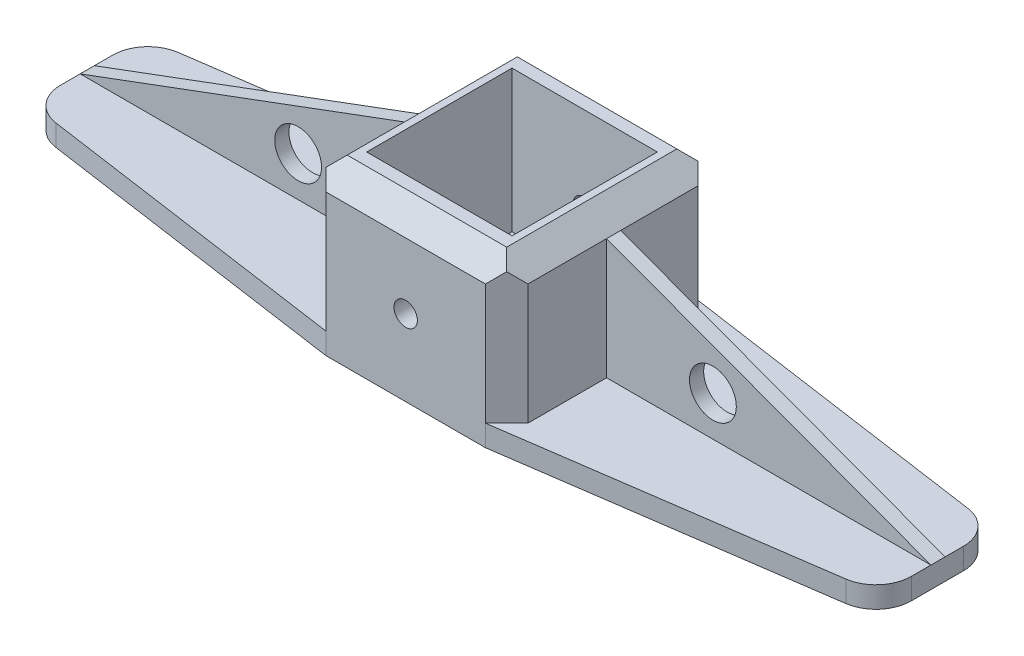
SolidWorks part; units mm, degrees
ref_plane "Front Plane" through (0, 0, 0) normal (0, 0, 1) x (1, 0, 0)
ref_plane "Top Plane" through (0, 0, 0) normal (0, 1, 0) x (1, 0, 0)
ref_plane "Right Plane" through (0, 0, 0) normal (1, 0, 0) x (0, 0, -1)
sketch "Sketch1" plane through (0, 0, 0) normal (0, 1, 0) x (1, 0, 0)
  line L1 (-60, 15) -> (60, 15)
  line L2 (-60, 15) -> (-60, -15)
  line L3 (-60, -15) -> (60, -15)
  line L4 (60, 15) -> (60, -15)
  line L5 (-60, 15) -> (60, -15) construction
  line L6 (-60, -15) -> (60, 15) construction
  point P0 (0, 0)
  dimension "D1" = 120
  dimension "D2" = 30
extrude "Boss-Extrude1" add sketch "Sketch1" along normal blind 3
sketch "Sketch2" plane through (0, 3, 0) normal (0, 1, 0) x (1, 0, 0)
  line L0 (60, 15) -> (-60, 15) construction
  line L1 (-10.25, 10.25) -> (10.25, 10.25)
  line L2 (-10.25, 10.25) -> (-10.25, -10.25)
  line L3 (-10.25, -10.25) -> (10.25, -10.25)
  line L4 (10.25, 10.25) -> (10.25, -10.25)
  line L5 (-10.25, 10.25) -> (10.25, -10.25) construction
  line L6 (-10.25, -10.25) -> (10.25, 10.25) construction
  line L7 (-14.25, -15) -> (14.25, -15)
  line L8 (-14.25, -15) -> (-14.25, 15)
  line L9 (-14.25, 15) -> (14.25, 15)
  line L10 (14.25, -15) -> (14.25, 15)
  line L11 (-14.25, -15) -> (14.25, 15) construction
  line L12 (-14.25, 15) -> (14.25, -15) construction
  point P0 (0, 0)
  point P6 (0, 0)
  dimension "D1" = 20.5
  dimension "D2" = 20.5
  dimension "D3" = 4
extrude "Boss-Extrude2" add sketch "Sketch2" along normal blind 20
chamfer "Chamfer1" distance 3 angle 45 4 edges at (14.25, 13, 15) (-14.25, 13, 15) (14.25, 13, -15) (-14.25, 13, -15)
chamfer "Chamfer2" distance 3 angle 45 4 edges at (0, 23, -15) (14.25, 23, 0) (-14.25, 23, 0) (0, 23, 15)
sketch "Sketch3" plane through (0, 3, 0) normal (0, 1, 0) x (1, 0, 0)
  line L0 (-11.25, 15) -> (-60, 8)
  line L1 (-60, 15) -> (-60, -15) construction
  line L2 (-60, 8) -> (-60, 15)
  line L3 (-60, 15) -> (-11.25, 15)
  line L4 (-11.25, -15) -> (-60, -8)
  line L5 (-60, -8) -> (-60, -15)
  line L6 (-60, -15) -> (-11.25, -15)
  line L7 (11.25, 15) -> (60, 15)
  line L8 (60, 15) -> (60, 8)
  line L9 (60, -15) -> (60, 15) construction
  line L10 (60, 8) -> (11.25, 15)
  line L11 (11.25, -15) -> (60, -15)
  line L12 (60, -15) -> (60, -8)
  line L13 (60, -8) -> (11.25, -15)
  dimension "D1" = 7
  dimension "D2" = 7
  dimension "D3" = 7
  dimension "D4" = 7
extrude "Cut-Extrude1" cut sketch "Sketch3" against normal blind 20
sketch "Sketch4" plane through (0, 0, 15) normal (0, 0, 1) x (1, 0, 0)
  circle A0 centre (0, 10.7357) radius 1.65
  dimension "D1" = 3.3
extrude "Cut-Extrude2" cut sketch "Sketch4" against normal blind 40
sketch "Sketch5" plane through (0, 3, 0) normal (0, 1, 0) x (1, 0, 0)
  line L1 (-9, -1) -> (-5.9161, -1)
  line L2 (-9, -1) -> (-9, 1)
  line L3 (-9, 1) -> (-5.9161, 1)
  line L4 (9, -1) -> (9, 1)
  line L7 (-1, -9) -> (1, -9)
  line L8 (-1, -9) -> (-1, -5.9161)
  line L9 (-1, 9) -> (1, 9)
  line L10 (1, -9) -> (1, -5.9161)
  line L11 (-1, -9) -> (-0.6626, -5.9633) construction
  line L13 (0.6626, -5.9633) -> (1, -9) construction
  line L20 (-1, 5.9161) -> (-1, 9)
  line L23 (1, 5.9161) -> (1, 9)
  line L24 (5.9161, 1) -> (9, 1)
  line L27 (5.9161, -1) -> (9, -1)
  arc A0 (1, -5.9161) -> (5.9161, -1) centre (0, 0) ccw
  arc A1 (5.9161, 1) -> (1, 5.9161) centre (0, 0) ccw
  arc A2 (-5.9161, -1) -> (-1, -5.9161) centre (0, 0) ccw
  arc A3 (-1, 5.9161) -> (-5.9161, 1) centre (0, 0) ccw
  dimension "D1" = 12
  dimension "D2" = 18
  dimension "D3" = 18
  dimension "D4" = 2
  dimension "D5" = 2
extrude "Cut-Extrude3" cut sketch "Sketch5" against normal blind 40
sketch "Sketch6" plane through (0, 3, 0) normal (0, 1, 0) x (1, 0, 0)
  line L0 (-14.25, 12) -> (-14.25, -12) construction
  line L1 (-14.25, 1.0871) -> (-60, 1.0871)
  line L2 (-14.25, 1.0871) -> (-14.25, -0.9129)
  line L3 (-14.25, -0.9129) -> (-60, -0.9129)
  line L4 (-60, 1.0871) -> (-60, -0.9129)
  line L5 (-60, 8) -> (-60, -8) construction
  line L6 (14.25, 12) -> (14.25, -12) construction
  line L7 (14.25, 1.0871) -> (60, 1.0871)
  line L8 (14.25, 1.0871) -> (14.25, -0.9129)
  line L9 (14.25, -0.9129) -> (60, -0.9129)
  line L10 (60, 1.0871) -> (60, -0.9129)
  line L11 (60, -8) -> (60, 8) construction
  point P16 (-14.25, 0.0871)
  point P17 (14.25, 0.0871)
  dimension "D1" = 1
  dimension "D2" = 1
  dimension "D3" = 0
extrude "Boss-Extrude3" add sketch "Sketch6" along normal blind 17
sketch "Sketch7" plane through (0, 0, 0.9129) normal (0, 0, 1) x (1, 0, 0)
  line L0 (-14.25, 20) -> (-60, 3)
  line L1 (-60, 3) -> (-66.0074, 26.9661)
  line L2 (-66.0074, 26.9661) -> (-14.25, 20)
  line L3 (14.25, 20) -> (60, 3)
  line L4 (60, 3) -> (71.0576, 29.3505)
  line L5 (71.0576, 29.3505) -> (14.25, 20)
extrude "Cut-Extrude5" cut sketch "Sketch7" against normal blind 17
sketch "Sketch8" plane through (0, 0, 0.9129) normal (0, 0, 1) x (1, 0, 0)
  line L0 (-14.25, 20) -> (-14.25, 3) construction
  line L1 (14.25, 20) -> (14.25, 3) construction
  circle A0 centre (-29.25, 8.6225) radius 3.302
  circle A1 centre (29.25, 8.6225) radius 3.302
  dimension "D1" = 6.604
  dimension "D2" = 15
  dimension "D3" = 6.604
  dimension "D4" = 15
extrude "Cut-Extrude6" cut sketch "Sketch8" against normal blind 17
fillet "Fillet1" radius 5 4 edges at (60, 1.5, -8) (60, 1.5, 8) (-60, 1.5, 8) (-60, 1.5, -8)
